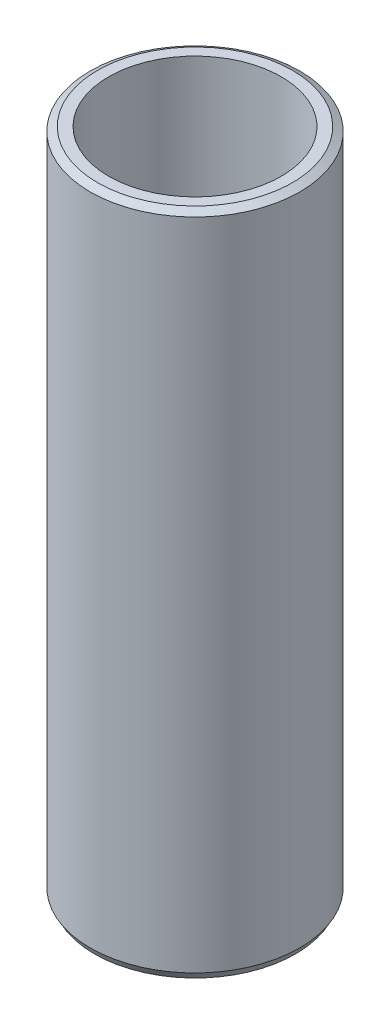
SolidWorks part; units mm, degrees
ref_plane "Front Plane" through (0, 0, 0) normal (0, 0, 1) x (1, 0, 0)
ref_plane "Top Plane" through (0, 0, 0) normal (0, 1, 0) x (1, 0, 0)
ref_plane "Right Plane" through (0, 0, 0) normal (1, 0, 0) x (0, 0, -1)
sketch "Sketch1" plane through (0, 0, 0) normal (0, 1, 0) x (1, 0, 0)
  circle A0 centre (0, 0) radius 40
  dimension "SHAFT_OD" = 80
extrude "Boss-Extrude1" add sketch "Sketch1" along normal blind 254.3151
sketch "Sketch2" plane through (0, 0, 0) normal (0, 1, 0) x (1, 0, 0)
  circle A0 centre (0, 0) radius 32.9292
  dimension "BORE_D" = 65.8585
extrude "Cut-Extrude1" cut sketch "Sketch2" along normal through all
chamfer "Chamfer1" distance 1.635 angle 60 2 edges at (0, 254.3151, 40) (0, 0, 40) first distance on face at (0, 254.3151, 40) first distance on face at (0, 0, 32.9292)
